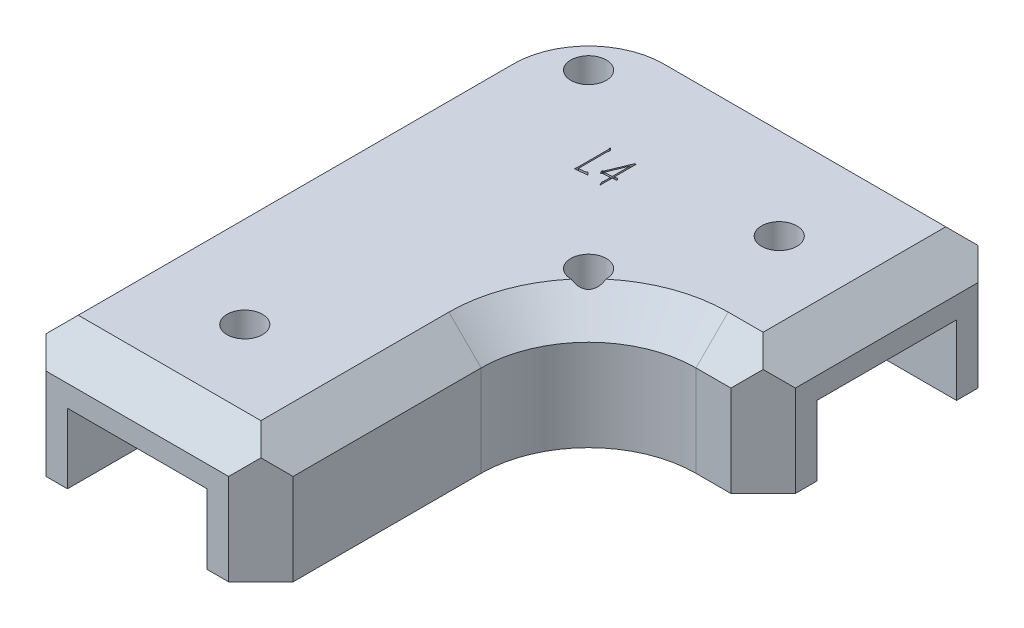
SolidWorks part; units mm, degrees
ref_plane "前视基准面" through (0, 0, 0) normal (0, 0, 1) x (1, 0, 0)
ref_plane "上视基准面" through (0, 0, 0) normal (0, 1, 0) x (1, 0, 0)
ref_plane "右视基准面" through (0, 0, 0) normal (1, 0, 0) x (0, 0, -1)
sketch "草图1" plane through (0, 0, 0) normal (0, 0, 1) x (1, 0, 0)
  line L1 (0, 0) -> (13, 0)
  line L2 (0, 0) -> (0, 13)
  line L3 (0, 13) -> (13, 13)
  line L4 (13, 0) -> (13, 13)
  line L5 (-5, 18) -> (18, 18)
  line L6 (-5, 18) -> (-5, -5)
  line L7 (-5, -5) -> (18, -5)
  line L8 (18, 18) -> (18, -5)
  dimension "D1" = 13
  dimension "D2" = 13
  dimension "D3" = 23
  dimension "D4" = 23
  dimension "D5" = 5
  dimension "D6" = 5
extrude "凸台-拉伸1" add sketch "草图1" along normal blind 53.5
sketch "草图2" plane through (0, -5, 0) normal (0, -1, 0) x (1, 0, 0)
  line L0 (-5, 53.5) -> (18, 53.5) construction
  line L1 (-5, 53.5) -> (-5, 0) construction
  circle A0 centre (6.5, 43.5) radius 1.65
  dimension "D1" = 3.3
  dimension "D2" = 10
  dimension "D3" = 11.5
extrude "切除-拉伸1" cut sketch "草图2" against normal blind 34
sketch "草图3" [suppressed] plane through (0, 25, 0) normal (0, 1, 0) x (1, 0, 0)
  line L0 (25, 0) -> (-5, 0) construction
  line L1 (2.5796, -2) -> (18.5796, -2)
  line L2 (2.5796, -2) -> (2.5796, -16)
  line L3 (2.5796, -16) -> (18.5796, -16)
  line L4 (18.5796, -2) -> (18.5796, -16)
  dimension "D1" = 14
  dimension "D2" = 2
  dimension "D3" = 16
sketch "草图4" plane through (18, 0, 0) normal (1, 0, 0) x (0, 0, -1)
  line L0 (-53.5, -5) -> (0, -5) construction
  line L1 (0, 18) -> (-23, 18)
  line L2 (0, 18) -> (0, -5)
  line L3 (0, -5) -> (-23, -5)
  line L4 (-23, 18) -> (-23, -5)
  circle A0 centre (-11.5, 6.5) radius 3
  dimension "D2" = 11.5
  dimension "D3" = 11.5
  dimension "D4" = 6
  dimension "D1" = 23
extrude "凸台-拉伸2" add sketch "草图4" along normal blind 6.25
sketch "草图5" plane through (24.25, 0, 0) normal (1, 0, 0) x (0, 0, -1)
  line L0 (0, -5) -> (0, 18) construction
  line L1 (-5, 0) -> (-18, 0)
  line L2 (-5, 0) -> (-5, 13)
  line L3 (-5, 13) -> (-18, 13)
  line L4 (-18, 0) -> (-18, 13)
  line L5 (-5, 0) -> (-18, 13) construction
  line L6 (-5, 13) -> (-18, 0) construction
  line L7 (-23, -5) -> (0, -5) construction
  point P0 (-11.5, 6.5)
  dimension "D1" = 13
  dimension "D2" = 13
  dimension "D3" = 5
  dimension "D4" = 5
extrude "拉伸-薄壁1" add sketch "草图5" along normal blind 10 thin thin type one direction wall 5
sketch "草图6" plane through (0, 18, 0) normal (0, 1, 0) x (1, 0, 0)
  line L0 (34.25, 0) -> (34.25, -23) construction
  line L1 (34.25, 0) -> (-5, 0) construction
  circle A0 centre (24.25, -11.5) radius 1.65
  dimension "D1" = 3.3
  dimension "D2" = 10
  dimension "D3" = 11.5
extrude "切除-拉伸2" cut sketch "草图6" against normal blind 39
sketch "草图7" plane through (24.25, 0, 0) normal (1, 0, 0) x (0, 0, -1)
  line L1 (-18, 13) -> (-5, 13)
  line L2 (-18, 13) -> (-18, 0)
  line L3 (-18, 0) -> (-5, 0)
  line L4 (-5, 13) -> (-5, 0)
extrude "切除-拉伸3" cut sketch "草图7" against normal blind 15.75
chamfer "倒角1" distance 3 angle 45 1 edges at (13, 6.5, 18)
chamfer "倒角2" [suppressed] distance 3 angle 45
sketch "草图8" plane through (0, -5, 0) normal (0, -1, 0) x (1, 0, 0)
  line L1 (-5, 53.5) -> (34.25, 53.5)
  line L2 (-5, 53.5) -> (-5, 0)
  line L3 (-5, 0) -> (34.25, 0)
  line L4 (34.25, 53.5) -> (34.25, 0)
extrude "切除-拉伸4" cut sketch "草图8" against normal blind 11.5
sketch "草图9" plane through (0, 13, 0) normal (0, -1, 0) x (1, 0, 0)
  line L0 (13, 5) -> (0, 18)
  line L2 (0, 18) -> (0, 0)
  line L3 (0, 0) -> (13, 0)
  line L4 (13, 0) -> (13, 5)
  dimension "D1" = 18
extrude "凸台-拉伸3" add sketch "草图9" along normal blind 6.5
fillet "圆角1" radius 10 1 edges at (-5, 12.25, 0)
fillet "圆角2" radius 10 1 edges at (18, 12.25, 23)
sketch "草图10" plane through (0, 6.5, 0) normal (0, -1, 0) x (1, 0, 0)
  line L0 (-5, 53.5) -> (-5, 10) construction
  line L1 (5, 0) -> (34.25, 0) construction
  line L2 (34.25, 18) -> (16, 18) construction
  line L3 (13, 21) -> (13, 53.5) construction
  circle A0 centre (2, 7) radius 1.65
  circle A1 centre (18, 23) radius 1.65
  dimension "D1" = 7
  dimension "D2" = 7
  dimension "D3" = 3.3
  dimension "D4" = 5
  dimension "D5" = 5
  dimension "D6" = 3.3
extrude "切除-拉伸5" cut sketch "草图10" against normal blind 28.5
chamfer "倒角3" distance 3 angle 45 6 edges at (18, 18, 43.25) (31.125, 18, 23) (20.9289, 18, 25.9289) (19.625, 18, 0) (-2.0711, 18, 2.9289) (-5, 18, 31.75)
chamfer "倒角4" distance 3 angle 45 2 edges at (34.25, 18, 11.5) (6.5, 18, 53.5)
chamfer "倒角5" distance 3 angle 45 4 edges at (34.25, 10.75, 0) (34.25, 10.75, 23) (18, 10.75, 53.5) (-5, 10.75, 53.5)
sketch "草图11" plane through (0, 18, 0) normal (0, 1, 0) x (1, 0, 0)
  text T0 "L4\r\n"
extrude "切除-拉伸6" cut sketch "草图11" against normal blind 0.3
